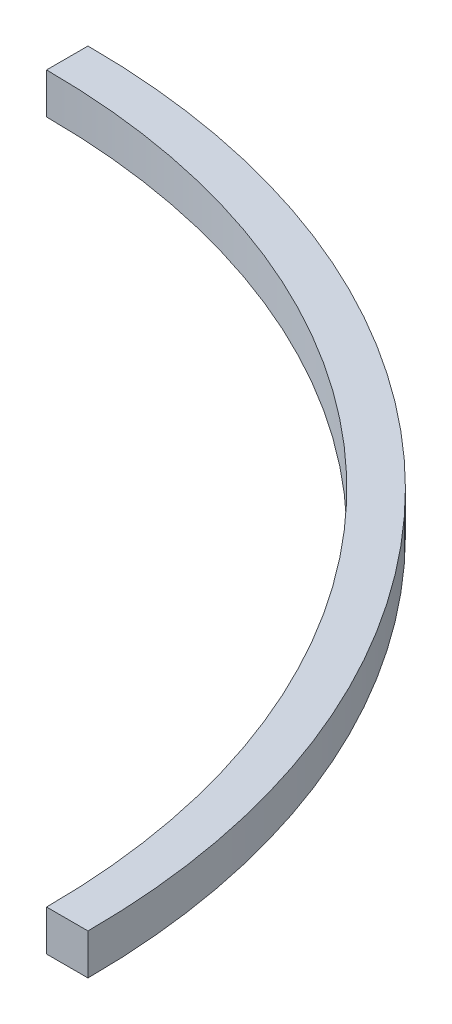
SolidWorks part; units mm, degrees
ref_plane "Front Plane" through (0, 0, 0) normal (0, 0, 1) x (1, 0, 0)
ref_plane "Top Plane" through (0, 0, 0) normal (0, 1, 0) x (1, 0, 0)
ref_plane "Right Plane" through (0, 0, 0) normal (1, 0, 0) x (0, 0, -1)
sketch "Sketch1" plane through (0, 0, 0) normal (0, 1, 0) x (1, 0, 0)
  line L0 (0, 0) -> (0, 470)
  line L1 (0, 0) -> (470, 0)
  circle A0 centre (0, 0) radius 470
  circle A1 centre (0, 0) radius 444.6
  dimension "D1" = 940
  dimension "D2" = 25.4
extrude "Boss-Extrude1" add sketch "Sketch1" along normal blind 25 contours A1 L1 A0 L0 region at (6.6468, 0, -457.3)
